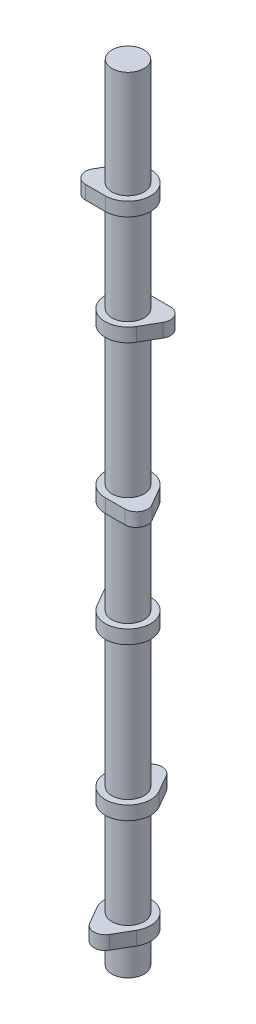
SolidWorks part; units mm, degrees
ref_plane "Front Plane" through (0, 0, 0) normal (1, 0, 0) x (0, 1, 0)
ref_plane "Top Plane" through (0, 0, 0) normal (0, 0, 1) x (0, 1, 0)
ref_plane "Right Plane" through (0, 0, 0) normal (0, 1, 0) x (-1, 0, 0)
sketch "Sketch6" plane through (0, 0, 0) normal (0, 1, 0) x (-1, 0, 0)
  line L0 (-5.4993, 15.875) -> (-10.9985, 6.35)
  line L1 (5.4993, 15.875) -> (10.9985, 6.35)
  arc A0 (-10.9985, 6.35) -> (10.9985, 6.35) centre (0, 0) ccw
  arc A1 (5.4993, 15.875) -> (-5.4993, 15.875) centre (0, 12.7) ccw
  dimension "D1" = 12.7
  dimension "D2" = 25.4
extrude "Boss-Extrude5" add sketch "Sketch6" along normal blind 7.62
ref_axis "Axis1" through (0, 442.1137, 0) along (0, -1, 0)
move or copy body "Body-Move/Copy2" bodies to move or copy 107 copy yes number of copies 1 translate (0, 60.9, 0) parameters "Distance Along Edge"=60.9
move or copy body "Body-Move/Copy3" bodies to move or copy 109 copy no rotation origin (0, 0, 0) rotation axis (0, 1, 0) rotation angle 180 parameters "Angle Around Edge"=180
sketch "Sketch7" plane through (0, 7.62, 0) normal (0, 1, 0) x (-1, 0, 0)
  circle A0 centre (0, 0) radius 9
  dimension "D1" = 18
extrude "Boss-Extrude7" add sketch "Sketch7" along normal blind 146.05 from offset 25.4 offset against normal yes
pattern_linear "LPattern1" count 3 spacing 146.05 along (0, 1, 0) of bodies 112
move or copy body "Body-Move/Copy4" bodies to move or copy 113 copy no rotation origin (0, 0, 0) rotation axis (0, -1, 0) rotation angle 120 parameters "Angle Around Edge"=120
move or copy body "Body-Move/Copy5" bodies to move or copy 114 copy no rotation origin (0, 0, 0) rotation axis (0, 1, 0) rotation angle 120 parameters "Angle Around Edge"=240
combine bodies "Combine1" operation type add bodies to combine 116 112 115
